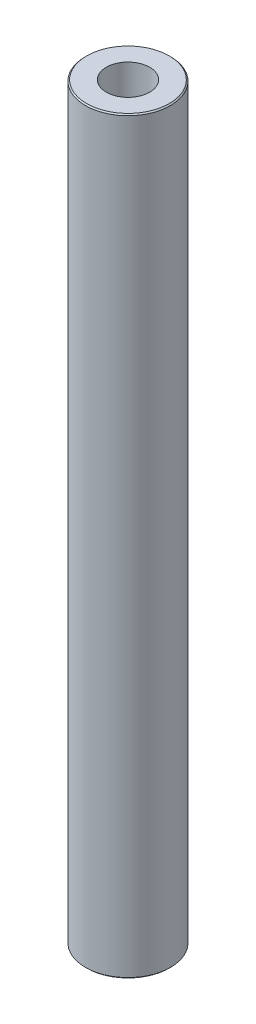
SolidWorks part; units mm, degrees
ref_plane "Front Plane" through (0, 0, 0) normal (0, 0, 1) x (1, 0, 0)
ref_plane "Top Plane" through (0, 0, 0) normal (0, 1, 0) x (1, 0, 0)
ref_plane "Right Plane" through (0, 0, 0) normal (1, 0, 0) x (0, 0, -1)
sketch "Sketch1" plane through (0, 0, 0) normal (0, 1, 0) x (1, 0, 0)
  circle A0 centre (0, 0) radius 10
  dimension "SHAFT_OD" = 20
extrude "Boss-Extrude1" add sketch "Sketch1" along normal blind 176.232
sketch "Sketch2" plane through (0, 0, 0) normal (0, 1, 0) x (1, 0, 0)
  circle A0 centre (0, 0) radius 5.1
  dimension "BORE_D" = 10.2
extrude "Cut-Extrude1" cut sketch "Sketch2" along normal through all
chamfer "Chamfer1" distance 0.277 angle 45.307 2 edges at (0, 176.232, 10) (0, 0, 10) first distance on face at (0, 176.232, 10) first distance on face at (0, 0, 5.1)
